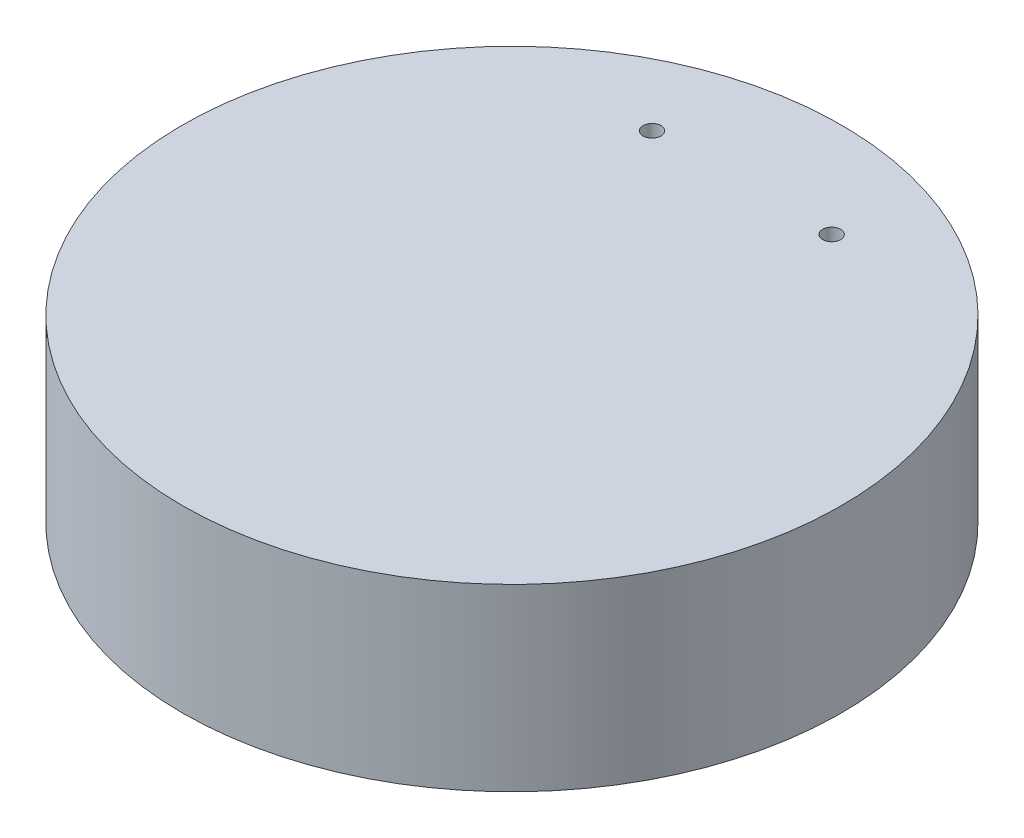
SolidWorks part; units mm, degrees
ref_plane "Front Plane" through (0, 0, 0) normal (0, 0, 1) x (1, 0, 0)
ref_plane "Top Plane" through (0, 0, 0) normal (0, 1, 0) x (1, 0, 0)
ref_plane "Right Plane" through (0, 0, 0) normal (1, 0, 0) x (0, 0, -1)
sketch "Sketch1" plane through (0, 0, 0) normal (0, 1, 0) x (1, 0, 0)
  circle A0 centre (0, 0) radius 46.609
  dimension "D1" = 93.218
extrude "Boss-Extrude1" add sketch "Sketch1" along normal blind 25.4
sketch "Sketch2" plane through (0, 25.4, 0) normal (0, 1, 0) x (1, 0, 0)
  circle A0 centre (0, 32.512) radius 4.9824
  circle A1 centre (12.7, 32.512) radius 1.27
  circle A2 centre (-12.7, 32.512) radius 1.27
  dimension "D4" = 2.54
  dimension "D5" = 2.54
  dimension "D1" = 32.512
  dimension "D2" = 0
  dimension "D3" = 0
  dimension "D6" = 12.7
  dimension "D7" = 12.7
extrude "Cut-Extrude1" cut sketch "Sketch2" against normal blind 25.4 contours A1 | A2 region at (12.7, 25.4, -32.512) region at (-12.7, 25.4, -32.512)
